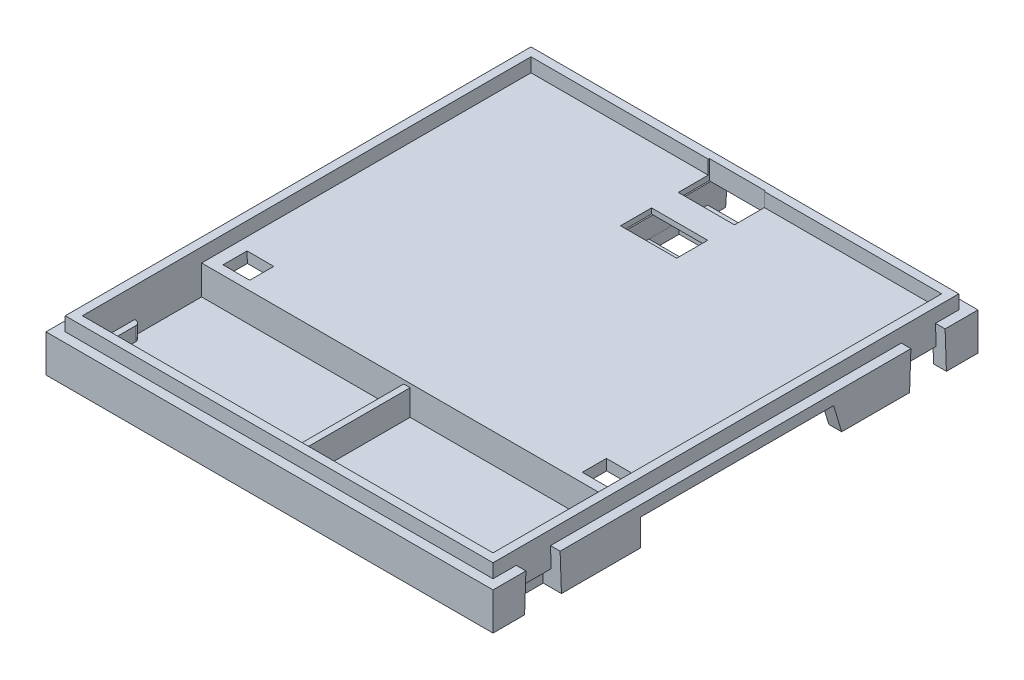
SolidWorks part; units mm, degrees
ref_plane "Спереди" through (0, 0, 0) normal (0, 0, 1) x (1, 0, 0)
ref_plane "Сверху" through (0, 0, 0) normal (0, 1, 0) x (1, 0, 0)
ref_plane "Справа" through (0, 0, 0) normal (1, 0, 0) x (0, 0, -1)
sketch "Эскиз1" plane through (0, 0, 0) normal (0, 1, 0) x (1, 0, 0)
  line L0 (0, 45.35) -> (0, -45.35) construction
  line L1 (41.8, -45.35) -> (-41.8, -45.35)
  line L2 (41.8, -45.35) -> (41.8, 45.35)
  line L3 (41.8, 45.35) -> (-41.8, 45.35)
  line L4 (-41.8, -45.35) -> (-41.8, 45.35)
  line L5 (41.8, -45.35) -> (-41.8, 45.35) construction
  line L6 (41.8, 45.35) -> (-41.8, -45.35) construction
  line L7 (-41.8, 0) -> (41.8, 0) construction
  point P0 (0, 0)
  dimension "D1" = 83.6
  dimension "D2" = 90.7
extrude "Бобышка-Вытянуть1" add sketch "Эскиз1" against normal blind 7
sketch "Эскиз2" plane through (0, 0, 0) normal (0, 1, 0) x (1, 0, 0)
  line L1 (40, -43.55) -> (-40, -43.55)
  line L2 (40, -43.55) -> (40, 43.55)
  line L3 (40, 43.55) -> (-40, 43.55)
  line L4 (-40, -43.55) -> (-40, 43.55)
  line L5 (40, -43.55) -> (-40, 43.55) construction
  line L6 (40, 43.55) -> (-40, -43.55) construction
  line L7 (38.4, -41.95) -> (-38.4, -41.95)
  line L8 (38.4, -41.95) -> (38.4, 41.95)
  line L9 (38.4, 41.95) -> (-38.4, 41.95)
  line L10 (-38.4, -41.95) -> (-38.4, 41.95)
  line L11 (38.4, -41.95) -> (-38.4, 41.95) construction
  line L12 (38.4, 41.95) -> (-38.4, -41.95) construction
  line L13 (-41.8, 45.35) -> (-41.8, -45.35) construction
  line L14 (41.8, 45.35) -> (-41.8, 45.35) construction
  line L15 (0, 0) -> (0, 45.35) construction
  line L16 (-5.25, 41.95) -> (-5.25, 42.15)
  line L17 (-5.25, 42.15) -> (5.25, 42.15)
  line L18 (5.25, 42.15) -> (5.25, 41.95)
  point P0 (0, 0)
  point P6 (0, 0)
  dimension "D1" = 1.8
  dimension "D2" = 1.8
  dimension "D3" = 1.6
  dimension "D4" = 1.6
  dimension "D5" = 10.5
  dimension "D6" = 0.2
extrude "Бобышка-Вытянуть2" add sketch "Эскиз2" along normal blind 2.6 contours L4 L1 L2 L3 L17 L18 L9 L8 L7 L10 L16 region at (0, 0, 42.3674)
sketch "Эскиз3" plane through (0, 0, 0) normal (0, 1, 0) x (1, 0, 0)
  line L0 (38.4, -41.95) -> (38.4, 41.95) construction
  line L1 (-38.4, -41.95) -> (38.4, -41.95)
  line L2 (-38.4, -41.95) -> (-38.4, -19.65)
  line L3 (-38.4, -19.65) -> (38.4, -19.65)
  line L4 (38.4, -41.95) -> (38.4, -19.65)
  dimension "D1" = 22.3
extrude "Вырез-Вытянуть1" cut sketch "Эскиз3" against normal blind 5.5
sketch "Эскиз4" plane through (0, -5.5, 0) normal (0, 1, 0) x (1, 0, 0)
  line L0 (38.4, -19.65) -> (-38.4, -19.65) construction
  line L1 (-0.6, -19.65) -> (0.6, -19.65)
  line L2 (-0.6, -19.65) -> (-0.6, -41.95)
  line L3 (-0.6, -41.95) -> (0.6, -41.95)
  line L4 (0.6, -19.65) -> (0.6, -41.95)
  line L5 (38.4, -41.95) -> (-38.4, -41.95) construction
  line L6 (0, 0) -> (0, -45.35) construction
  line L7 (-41.8, -45.35) -> (41.8, -45.35) construction
  dimension "D1" = 1.2
extrude "Бобышка-Вытянуть3" add sketch "Эскиз4" along normal blind 4.8
sketch "Эскиз5" plane through (0, -5.5, 0) normal (0, 1, 0) x (1, 0, 0)
  line L0 (0, 0) -> (0, -45.35) construction
  line L1 (-41.8, -45.35) -> (41.8, -45.35) construction
  line L2 (38.4, -41.95) -> (-38.4, -41.95) construction
  line L3 (-9.45, -41.95) -> (-10.55, -41.95)
  line L4 (-9.45, -41.95) -> (-9.45, -39.95)
  line L5 (-9.45, -39.95) -> (-10.55, -39.95)
  line L6 (-10.55, -41.95) -> (-10.55, -39.95)
  line L8 (-28.6, -41.95) -> (-29.7, -41.95)
  line L9 (-28.6, -41.95) -> (-28.6, -39.95)
  line L10 (-28.6, -39.95) -> (-29.7, -39.95)
  line L11 (-29.7, -41.95) -> (-29.7, -39.95)
  line L12 (9.45, -41.95) -> (10.55, -41.95)
  line L13 (9.45, -41.95) -> (9.45, -39.95)
  line L14 (9.45, -39.95) -> (10.55, -39.95)
  line L15 (10.55, -41.95) -> (10.55, -39.95)
  line L16 (28.6, -41.95) -> (29.7, -41.95)
  line L17 (28.6, -41.95) -> (28.6, -39.95)
  line L18 (28.6, -39.95) -> (29.7, -39.95)
  line L19 (29.7, -41.95) -> (29.7, -39.95)
  dimension "D1" = 1.1
  dimension "D2" = 5.4
  dimension "D3" = 21.1
  dimension "D4" = 57.2
extrude "Бобышка-Вытянуть4" add sketch "Эскиз5" along normal blind 4.7
sketch "Эскиз6" plane through (0, -5.5, 0) normal (0, 1, 0) x (1, 0, 0)
  line L0 (0, 0) -> (0, -45.35) construction
  line L1 (-41.8, -45.35) -> (41.8, -45.35) construction
  line L2 (-38.4, -32.15) -> (-38.3, -32.15)
  line L4 (-38.4, -41.95) -> (-38.4, 41.95) construction
  line L5 (-37.3, -33.15) -> (-37.3, -38.85)
  line L6 (38.4, -32.15) -> (38.3, -32.15)
  line L7 (38.4, -41.95) -> (38.4, 41.95) construction
  line L8 (37.3, -33.15) -> (37.3, -38.85)
  line L9 (38.3, -39.85) -> (38.4, -39.85)
  line L10 (-38.3, -39.85) -> (-38.4, -39.85)
  line L11 (-41.8, 45.35) -> (-41.8, -45.35) construction
  line L12 (-38.4, -32.15) -> (-38.4, -39.85)
  line L13 (38.4, -32.15) -> (38.4, -39.85)
  line L21 (-41.8, -36) -> (-36.0571, -36) construction
  arc A0 (37.3, -38.85) -> (38.3, -39.85) centre (38.3, -38.85) ccw
  arc A1 (38.3, -32.15) -> (37.3, -33.15) centre (38.3, -33.15) ccw
  arc A2 (-37.3, -38.85) -> (-38.3, -39.85) centre (-38.3, -38.85) cw
  arc A3 (-37.3, -33.15) -> (-38.3, -32.15) centre (-38.3, -33.15) ccw
  point P27 (-37.3, -36)
  dimension "D3" = 1
  dimension "D1" = 7.7
  dimension "D2" = 4.5
  dimension "D4" = 9.35
extrude "Бобышка-Вытянуть5" add sketch "Эскиз6" along normal blind 2.6
sketch "Эскиз7" plane through (-41.8, 0, 0) normal (-1, 0, 0) x (0, 0, 1)
  line L0 (0, 2.6) -> (0, -7) construction
  line L1 (43.55, 2.6) -> (-43.55, 2.6) construction
  line L2 (-45.35, -7) -> (45.35, -7) construction
  line L3 (-39.2, 0) -> (-39.4444, -7)
  line L4 (-45.35, 0) -> (45.35, 0) construction
  line L5 (-39.2, 0) -> (-32.8, 0)
  line L6 (-32.8, 0) -> (-32.5556, -7)
  line L7 (-32.5556, -7) -> (-39.4444, -7)
  line L8 (32.5556, -7) -> (32.8, 0)
  line L9 (32.8, 0) -> (39.2, 0)
  line L10 (39.2, 0) -> (39.4444, -7)
  line L11 (39.4444, -7) -> (32.5556, -7)
  line L12 (36, 1.1548) -> (36, -8.4691) construction
  line L13 (45.35, -7) -> (45.35, 0) construction
  point P20 (36, 0)
  dimension "D1" = 92
  dimension "D2" = 9.35
  dimension "D3" = 6.4
extrude "Вырез-Вытянуть2" cut sketch "Эскиз7" against normal blind 1.8
mirror "Зеркальное отражение2" about plane through (0, 0, 0) normal (1, 0, 0) of "Вырез-Вытянуть2"
sketch "Эскиз8" plane through (0, -7, 0) normal (0, -1, 0) x (1, 0, 0)
  line L0 (-41.8, 17.75) -> (41.8, 17.75)
  line L1 (-41.8, -32.5556) -> (-41.8, 32.5556) construction
  line L2 (41.8, 32.5556) -> (41.8, -32.5556) construction
  line L3 (41.8, 17.75) -> (41.8, -18.35)
  line L4 (41.8, -18.35) -> (39.4, -18.35)
  line L5 (39.4, -18.35) -> (39.4, -43.35)
  line L6 (39.4, -43.35) -> (7.1, -43.35)
  line L7 (7.1, -43.35) -> (7.1, -24.75)
  line L8 (7.1, -24.75) -> (-7.1, -24.75)
  line L9 (-7.1, -24.75) -> (-7.1, -43.35)
  line L10 (-7.1, -43.35) -> (-39.4, -43.35)
  line L11 (-39.4, -43.35) -> (-39.4, -18.35)
  line L12 (-39.4, -18.35) -> (-41.8, -18.35)
  line L13 (-41.8, -18.35) -> (-41.8, 17.75)
  line L14 (0, 45.35) -> (0, -45.35) construction
  line L15 (-41.8, 45.35) -> (41.8, 45.35) construction
  line L16 (41.8, -45.35) -> (-41.8, -45.35) construction
  dimension "D1" = 27.6
  dimension "D2" = 14.2
  dimension "D3" = 42.5
  dimension "D4" = 27
  dimension "D5" = 2
  dimension "D6" = 2.4
extrude "Вырез-Вытянуть3" cut sketch "Эскиз8" against normal blind 5
sketch "Эскиз9" plane through (0, 0, -45.35) normal (0, 0, -1) x (-1, 0, 0)
  line L0 (0, 2.6) -> (0, -7) construction
  line L1 (-40, 2.6) -> (40, 2.6) construction
  line L2 (-41.8, -7) -> (41.8, -7) construction
  line L3 (-5, -1) -> (5, -1)
  line L4 (5, -1) -> (5.25, -4.8)
  line L5 (5.25, -4.8) -> (-5.25, -4.8)
  line L6 (-5.25, -4.8) -> (-5, -1)
  dimension "D1" = 3.6
  dimension "D2" = 2.2
  dimension "D3" = 10
  dimension "D4" = 10.5
extrude "Вырез-Вытянуть4" cut sketch "Эскиз9" against normal blind 52
sketch "Эскиз10" plane through (0, 0, -45.35) normal (0, 0, -1) x (-1, 0, 0)
  line L0 (-5.25, -4.8) -> (5.25, -4.8)
  line L1 (5.25, -4.8) -> (5.3947, -7)
  line L2 (-41.8, -7) -> (41.8, -7) construction
  line L3 (-5.3947, -7) -> (5.3947, -7)
  line L4 (-5.3947, -7) -> (-5.25, -4.8)
  line L5 (-5, -1) -> (-5.25, -4.8) construction
  line L6 (5.25, -4.8) -> (5, -1) construction
extrude "Вырез-Вытянуть5" cut sketch "Эскиз10" against normal blind 3.5
sketch "Эскиз11" plane through (40, 0, 0) normal (1, 0, 0) x (0, 0, -1)
  line L0 (32.5556, -7) -> (39.4444, -7)
  line L1 (39.4444, -7) -> (39.2698, -2)
  line L2 (39.2, 0) -> (39.4444, -7) construction
  line L3 (39.2698, -2) -> (32.7302, -2)
  line L4 (32.5556, -7) -> (32.8, 0) construction
  line L5 (32.7302, -2) -> (32.5556, -7)
  line L6 (43.35, -2) -> (18.35, -2) construction
extrude "Вырез-Вытянуть6" cut sketch "Эскиз11" against normal blind 0.6
sketch "Эскиз12" plane through (0, -2, 0) normal (0, -1, 0) x (1, 0, 0)
  line L0 (40, -39.2698) -> (40, -32.7302) construction
  line L1 (39.4, -31.7) -> (40, -31.7)
  line L2 (38.4, -32.7) -> (38.4, -39.3)
  line L3 (39.4, -40.3) -> (40, -40.3)
  line L4 (40, -31.7) -> (40, -40.3)
  line L5 (41.8, -18.35) -> (41.8, -32.5556) construction
  line L6 (41.8, -32.8) -> (41.8, -39.2) construction
  line L7 (41.8, -36) -> (34.0886, -36) construction
  arc A0 (38.4, -39.3) -> (39.4, -40.3) centre (39.4, -39.3) ccw
  arc A1 (39.4, -31.7) -> (38.4, -32.7) centre (39.4, -32.7) ccw
  point P16 (38.4, -40.3)
  point P19 (38.4, -31.7)
  dimension "D3" = 1
  dimension "D1" = 8.6
  dimension "D2" = 3.4
extrude "Бобышка-Вытянуть6" add sketch "Эскиз12" along normal blind 1.8
sketch "Эскиз13" plane through (-7.1, 0, 0) normal (-1, 0, 0) x (0, 0, 1)
  line L0 (-24.75, -7) -> (-24.75, -2)
  line L1 (-24.75, -2) -> (-25.25, -7)
  line L2 (-24.75, -7) -> (-43.35, -7) construction
  line L3 (-25.25, -7) -> (-24.75, -7)
  dimension "D1" = 0.5
extrude "Вырез-Вытянуть7" cut sketch "Эскиз13" against normal up to surface (14.2 mm away) up to face at (7.1, -4.5, -34.05)
sketch "Эскиз14" plane through (40, 0, 0) normal (1, 0, 0) x (0, 0, -1)
  line L0 (-39.4444, -7) -> (-32.5556, -7)
  line L1 (-32.5556, -7) -> (-32.6673, -3.8)
  line L2 (-32.8, 0) -> (-32.5556, -7) construction
  line L3 (-32.6673, -3.8) -> (-39.3327, -3.8)
  line L4 (-39.4444, -7) -> (-39.2, 0) construction
  line L5 (-39.3327, -3.8) -> (-39.4444, -7)
  line L6 (39.3327, -3.8) -> (32.6673, -3.8) construction
extrude "Вырез-Вытянуть8" cut sketch "Эскиз14" against normal up to surface (1.6 mm away) up to face at (38.4, -2.9, -36)
mirror "Зеркальное отражение3" about plane through (0, 0, 0) normal (1, 0, 0) of "Вырез-Вытянуть8", "Вырез-Вытянуть6", "Бобышка-Вытянуть6"
sketch "Эскиз15" plane through (0, -2, 0) normal (0, -1, 0) x (1, 0, 0)
  line L0 (0, 17.75) -> (0, 6.65) construction
  line L1 (41.8, 17.75) -> (-41.8, 17.75) construction
  line L2 (-5.0658, 6.65) -> (5.0658, 6.65) construction
  line L3 (-26.3, 14.55) -> (-11.3, 14.55) construction
  line L4 (-26.3, 15.55) -> (-11.3, 15.55)
  line L5 (-26.3, 13.55) -> (-11.3, 13.55)
  line L6 (11.3, 14.55) -> (26.3, 14.55) construction
  line L7 (11.3, 15.55) -> (26.3, 15.55)
  line L8 (11.3, 13.55) -> (26.3, 13.55)
  arc A0 (-26.3, 15.55) -> (-26.3, 13.55) centre (-26.3, 14.55) ccw
  arc A1 (-11.3, 13.55) -> (-11.3, 15.55) centre (-11.3, 14.55) ccw
  arc A2 (11.3, 15.55) -> (11.3, 13.55) centre (11.3, 14.55) ccw
  arc A3 (26.3, 13.55) -> (26.3, 15.55) centre (26.3, 14.55) ccw
  point P8 (-18.8, 14.55)
  point P13 (18.8, 14.55)
  point P20 (10.3, 14.55)
  point P21 (-10.3, 14.55)
  point P23 (-27.3, 14.55)
  dimension "D2" = 20.6
  dimension "D1" = 2
  dimension "D3" = 17
  dimension "D4" = 2.2
extrude "Бобышка-Вытянуть7" add sketch "Эскиз15" along normal blind 0.7
sketch "Эскиз16" plane through (0, -2, 0) normal (0, -1, 0) x (1, 0, 0)
  line L0 (0, 6.65) -> (0, -25.03) construction
  line L1 (-5.0658, 6.65) -> (5.0658, 6.65) construction
  line L2 (-5.25, -25.03) -> (5.25, -25.03) construction
  line L3 (-13.6, -23.35) -> (-13.6, -23.85) construction
  line L4 (-12.1, -23.35) -> (-12.1, -23.85)
  line L5 (-15.1, -23.35) -> (-15.1, -23.85)
  line L6 (13.6, -23.35) -> (13.6, -23.85) construction
  line L7 (15.1, -23.35) -> (15.1, -23.85)
  line L8 (12.1, -23.35) -> (12.1, -23.85)
  line L9 (-39.4, -43.35) -> (-7.1, -43.35) construction
  arc A0 (-12.1, -23.35) -> (-15.1, -23.35) centre (-13.6, -23.35) ccw
  arc A1 (-15.1, -23.85) -> (-12.1, -23.85) centre (-13.6, -23.85) ccw
  arc A2 (15.1, -23.35) -> (12.1, -23.35) centre (13.6, -23.35) ccw
  arc A3 (12.1, -23.85) -> (15.1, -23.85) centre (13.6, -23.85) ccw
  point P8 (-13.6, -23.6)
  point P13 (13.6, -23.6)
  point P21 (-13.6, -21.85)
  point P22 (-13.6, -25.35)
  dimension "D1" = 3
  dimension "D2" = 3.5
  dimension "D3" = 30.2
  dimension "D4" = 18
extrude "Бобышка-Вытянуть8" add sketch "Эскиз16" along normal blind 3
sketch "Эскиз17" plane through (0, 0, 0) normal (0, 1, 0) x (1, 0, 0)
  line L0 (5.25, 42.15) -> (5.25, 41.95) construction
  line L1 (-5.25, 42.15) -> (5.25, 42.15)
  line L2 (-5.25, 42.15) -> (-5.25, 36.35)
  line L3 (-5.25, 36.35) -> (5.25, 36.35)
  line L4 (5.25, 42.15) -> (5.25, 36.35)
  line L5 (-5.25, 31.35) -> (5.25, 31.35)
  line L6 (-5.25, 31.35) -> (-5.25, 25.55)
  line L7 (-5.25, 25.55) -> (5.25, 25.55)
  line L8 (5.25, 31.35) -> (5.25, 25.55)
  dimension "D1" = 5.8
  dimension "D2" = 5
extrude "Вырез-Вытянуть9" cut sketch "Эскиз17" against normal up to surface (1 mm away) up to face at (0, -1, -19.35)
sketch "Эскиз18" plane through (0, -7, 0) normal (0, -1, 0) x (1, 0, 0)
  line L0 (-5.3947, -41.85) -> (-5.3947, -45.35) construction
  line L1 (-5.3947, -36.65) -> (5.3947, -36.65)
  line L2 (-5.3947, -36.65) -> (-5.3947, -30.85)
  line L3 (-5.3947, -30.85) -> (5.3947, -30.85)
  line L4 (5.3947, -36.65) -> (5.3947, -30.85)
  line L5 (5.3947, -41.85) -> (5.3947, -45.35) construction
  line L6 (5.3947, -41.85) -> (-5.3947, -41.85) construction
  dimension "D1" = 5.8
  dimension "D2" = 5.2
extrude "Вырез-Вытянуть10" cut sketch "Эскиз18" against normal up to surface (2.2 mm away) up to face at (0, -4.8, -33.44)
sketch "Эскиз19" plane through (41.8, 0, 0) normal (1, 0, 0) x (0, 0, -1)
  line L0 (18.35, -2) -> (18.35, -7)
  line L1 (18.35, -7) -> (19.85, -7)
  line L2 (18.35, -7) -> (32.5556, -7) construction
  line L3 (19.85, -7) -> (18.35, -2)
  dimension "D1" = 1.5
extrude "Вырез-Вытянуть11" cut sketch "Эскиз19" against normal through all
sketch "Эскиз20" plane through (0, 0, 17.75) normal (0, 0, -1) x (-1, 0, 0)
  line L0 (-36.1, 0) -> (-35.9, -7)
  line L1 (-38.4, 0) -> (38.4, 0) construction
  line L2 (-41.8, -7) -> (41.8, -7) construction
  line L3 (-35.9, -7) -> (-31.3, -7)
  line L4 (-31.3, -7) -> (-31.1, 0)
  line L5 (-31.1, 0) -> (-36.1, 0)
  line L6 (31.1, 0) -> (31.3, -7)
  line L7 (31.3, -7) -> (35.9, -7)
  line L8 (35.9, -7) -> (36.1, 0)
  line L9 (36.1, 0) -> (31.1, 0)
  line L10 (0, -7) -> (0, 2.6) construction
  line L11 (-38.4, 2.6) -> (38.4, 2.6) construction
  dimension "D1" = 4.6
  dimension "D2" = 5
  dimension "D3" = 62.2
extrude "Вырез-Вытянуть12" cut sketch "Эскиз20" against normal blind 0.2 and the other way blind 4.3
ref_plane "Плоскость1" through (-33.6, -6, 0) normal (1, 0, 0) x (0, 0, -1)
sketch "Эскиз22" plane through (-33.6, -6, 0) normal (1, 0, 0) x (0, 0, -1)
  line L0 (-17.95, -1) -> (-17.95, 2.8)
  line L1 (-17.95, -1) -> (-17.95, 6) construction
  line L2 (-17.95, 2.8) -> (-15.35, 2.2)
  line L3 (-15.35, 2.2) -> (-15.35, -1)
  line L4 (-15.35, -1) -> (-17.95, -1)
  line L5 (-17.75, -1) -> (-17.75, 4) construction
  dimension "D1" = 3.8
  dimension "D2" = 2.4
  dimension "D3" = 3.2
extrude "Бобышка-Вытянуть10" add sketch "Эскиз22" along normal mid plane 1.8
sketch "Эскиз24" plane through (-33.6, -6, 0) normal (1, 0, 0) x (0, 0, -1)
  line L0 (-17.95, 2.6) -> (-15.25, 1)
  line L1 (-17.95, -1) -> (-17.95, 6) construction
  line L2 (-15.25, 1) -> (-15.25, -1)
  line L3 (-15.25, -1) -> (-17.95, -1)
  line L4 (-17.95, -1) -> (-17.95, 2.6)
  line L5 (-17.75, -1) -> (-17.75, 4) construction
  dimension "D1" = 2.5
  dimension "D2" = 2
  dimension "D3" = 3.6
extrude "Бобышка-Вытянуть11" add sketch "Эскиз24" along normal mid plane 5
sketch "Эскиз25" plane through (0, 0, 17.75) normal (0, 0, -1) x (-1, 0, 0)
  line L0 (31.1971, -3.4) -> (31.3, -7)
  line L1 (41.8, -7) -> (-41.8, -7) construction
  line L2 (31.3, -7) -> (30.4975, -7)
  line L3 (-31.3, -7) -> (31.1, -7) construction
  line L4 (30.4975, -7) -> (30.4975, -3.4)
  line L5 (30.4975, -3.4) -> (31.1971, -3.4)
  line L6 (36.0029, -3.4) -> (35.9, -7)
  line L7 (35.9, -7) -> (36.7416, -7)
  line L8 (36.1, -7) -> (41.8, -7) construction
  line L9 (36.7416, -7) -> (36.7416, -3.4)
  line L10 (36.7416, -3.4) -> (36.0029, -3.4)
extrude "Вырез-Вытянуть13" cut sketch "Эскиз25" along normal blind 5
mirror "Зеркальное отражение4" about plane through (0, 0, 0) normal (1, 0, 0) of "Бобышка-Вытянуть11", "Вырез-Вытянуть13", "Бобышка-Вытянуть10"
